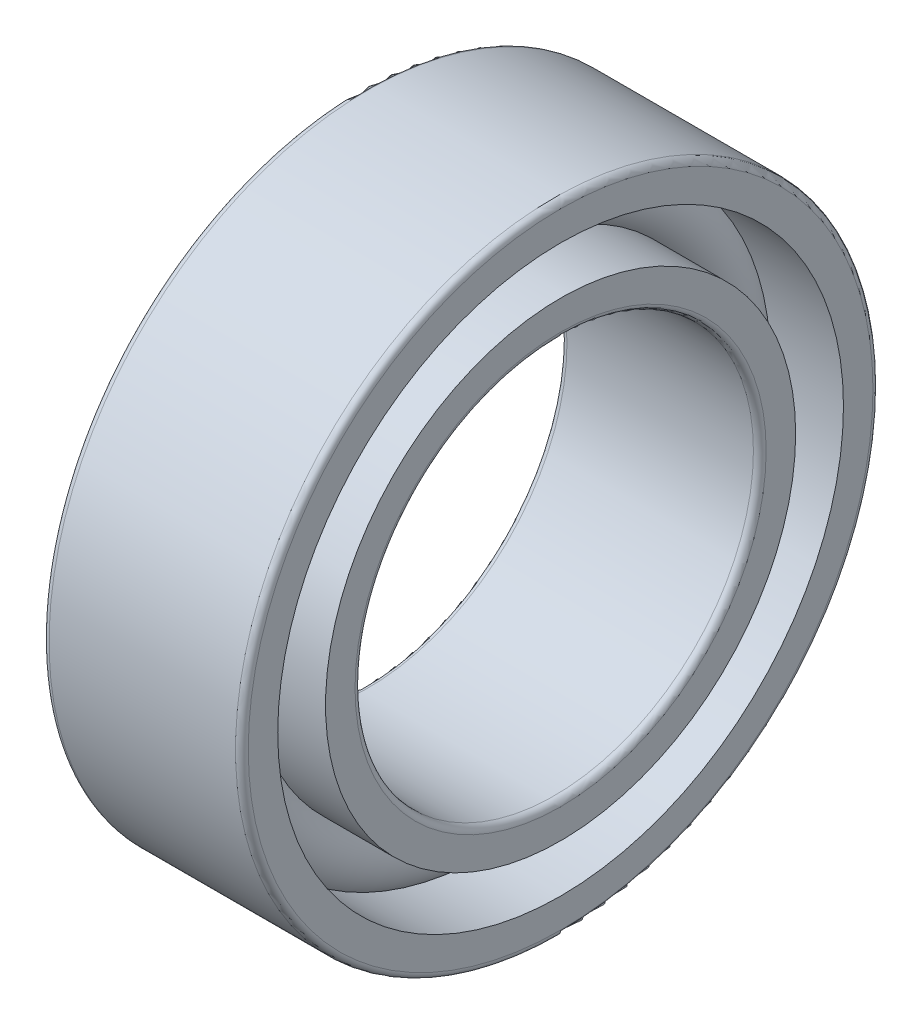
SolidWorks part; units mm, degrees
ref_plane "Plane1" through (0, 0, 0) normal (0, 0, 1) x (1, 0, 0)
ref_plane "Plane2" through (0, 0, 0) normal (0, 1, 0) x (1, 0, 0)
ref_plane "Plane3" through (0, 0, 0) normal (1, 0, 0) x (0, 0, -1)
sketch "Clipboard" plane through (0, 0, 0) normal (0, 0, 1) x (1, 0, 0)
  line L0 (-10, 0) -> (10, 0) construction
  line L1 (0, 0) -> (22.3471, -0.7804)
  line L2 (0, 0) -> (3.248, 0.1134)
  line L3 (0, 0) -> (22.3471, -0.7804)
  line L4 (0, 0) -> (-22.3573, -0.3902)
  dimension "BallCLRad" = 3.25
sketch "CagSpiSke" plane through (0, 0, 0) normal (0, 0, 1) x (1, 0, 0)
  line L0 (0.045, 3.175) -> (0.045, 3.325)
  line L1 (0.045, 3.325) -> (-0.045, 3.325)
  line L2 (-0.045, 3.325) -> (-0.045, 3.175)
  line L3 (-0.045, 3.175) -> (0.045, 3.175)
  line L4 (-20.6375, 0) -> (20.6375, 0) construction
  line L5 (0, 0) -> (0, 23.7692) construction
  dimension "OD" = 6.65
  dimension "ID" = 6.35
revolve "CageSpine" add sketch "CagSpiSke" angle 0.001 about L4 reverse direction yes
ref_axis "Axis1" through (-50, 0, 0) along (1, 0, 0)
sketch "CagBalSke" plane through (0, 0, 0) normal (0, 0, 1) x (1, 0, 0)
  line L0 (-0.495, 3.25) -> (0.495, 3.25)
  line L1 (-1.905, 3.25) -> (1.905, 3.25) construction
  line L2 (-10, 0) -> (10, 0) construction
  line L3 (0, 0) -> (0, 24) construction
  arc A0 (0.495, 3.25) -> (-0.495, 3.25) centre (0, 3.25) cw
  dimension "BallCLRad" = 3.25
revolve "CageBall" [suppressed] add sketch "CagBalSke" angle 360 about L1 reverse direction yes
pattern_circular "CageBalls" [suppressed] count 2 every 180 about axis through (-50, 0, 0) along (1, 0, 0)
sketch "CagTrmODSke" plane through (0, 0, 0) normal (0, 0, 1) x (1, 0, 0)
  line L0 (0.496, 3.325) -> (0.496, 3.746)
  line L1 (0.496, 3.746) -> (-0.496, 3.746)
  line L2 (-0.496, 3.746) -> (-0.496, 3.325)
  line L3 (-0.496, 3.325) -> (0.496, 3.325)
  line L4 (-20.6375, 0) -> (20.6375, 0) construction
  line L5 (0, 0) -> (0, 25) construction
  dimension "Width" = 0.992
  dimension "ID" = 6.65
  dimension "OD" = 7.492
revolve "CageTrimOD" [suppressed] cut sketch "CagTrmODSke" angle 360 about L4 reverse direction yes
sketch "CagTrmIDSke" plane through (0, 0, 0) normal (0, 0, 1) x (1, 0, 0)
  line L0 (0.496, 2.756) -> (0.496, 3.175)
  line L1 (0.496, 3.175) -> (-0.496, 3.175)
  line L2 (-0.496, 3.175) -> (-0.496, 2.756)
  line L3 (-0.496, 2.756) -> (0.496, 2.756)
  line L4 (-20.6375, 0) -> (20.6375, 0) construction
  line L5 (0, 0) -> (0, 25) construction
  dimension "Width" = 0.992
  dimension "ID" = 5.512
  dimension "OD" = 6.35
revolve "CageTrimID" [suppressed] cut sketch "CagTrmIDSke" angle 360 about L4 reverse direction yes
sketch "BalSimSke" plane through (0, 0, 0) normal (0, 0, 1) x (1, 0, 0)
  line L0 (-10, 0) -> (10, 0) construction
  line L1 (-10, 3.25) -> (10, 3.25) construction
  line L2 (0, 0) -> (0, 23) construction
  circle A0 centre (0, 3.25) radius 0.45
  dimension "BallCLRad" = 3.25
  dimension "Ball_diameter" = 0.9
revolve "BallsSimplified" add sketch "BalSimSke" angle 360 about L0
sketch "BalDetSke" plane through (0, 0, 0) normal (0, 0, 1) x (1, 0, 0)
  line L0 (-0.45, 3.25) -> (0.45, 3.25)
  line L1 (-1.905, 3.25) -> (1.905, 3.25) construction
  line L2 (0, 0) -> (0, 25) construction
  arc A0 (0.45, 3.25) -> (-0.45, 3.25) centre (0, 3.25) cw
  dimension "BallCLRad" = 3.25
  dimension "Ball_diameter" = 0.9
revolve "BallDetailed" [suppressed] add sketch "BalDetSke" angle 360 about L1 reverse direction yes
sketch "InnRacSke" plane through (0, 0, 0) normal (0, 0, 1) x (1, 0, 0)
  line L0 (-0.301, 2.95) -> (-1.25, 2.95)
  line L1 (-1.25, 2.95) -> (-1.25, 2.58)
  line L2 (-1.17, 2.5) -> (1.17, 2.5)
  line L3 (1.25, 2.58) -> (1.25, 2.95)
  line L4 (1.25, 2.95) -> (0.301, 2.95)
  line L5 (-20.6375, 0) -> (20.6375, 0) construction
  line L6 (0, 0) -> (0, 30) construction
  arc A0 (-1.25, 2.58) -> (-1.17, 2.5) centre (-1.17, 2.58) ccw
  arc A1 (1.17, 2.5) -> (1.25, 2.58) centre (1.17, 2.58) ccw
  arc A2 (0.301, 2.95) -> (-0.301, 2.95) centre (0, 3.25) cw
  dimension "BallCLRad" = 3.25
  dimension "Fillet_radius" = 0.08
  dimension "Ball_diameter" = 0.85
  dimension "ID" = 5
  dimension "OD" = 5.9
  dimension "Width" = 2.5
revolve "InnerRace" add sketch "InnRacSke" angle 360 about L5 reverse direction yes
sketch "OutRacSke" plane through (0, 0, 0) normal (0, 0, 1) x (1, 0, 0)
  line L0 (-0.301, 3.55) -> (-1.25, 3.55)
  line L1 (-1.25, 3.55) -> (-1.25, 3.92)
  line L2 (-1.17, 4) -> (1.17, 4)
  line L3 (1.25, 3.92) -> (1.25, 3.55)
  line L4 (1.25, 3.55) -> (0.301, 3.55)
  line L5 (-20.6375, 0) -> (20.6375, 0) construction
  line L6 (0, 0) -> (0, 30) construction
  arc A0 (-1.25, 3.92) -> (-1.17, 4) centre (-1.17, 3.92) cw
  arc A1 (1.17, 4) -> (1.25, 3.92) centre (1.17, 3.92) cw
  arc A2 (0.301, 3.55) -> (-0.301, 3.55) centre (0, 3.25) ccw
  dimension "BallCLRad" = 3.25
  dimension "Fillet_radius" = 0.08
  dimension "Ball_diameter" = 0.85
  dimension "Width" = 2.5
revolve "OuterRace" add sketch "OutRacSke" angle 360 about L5 reverse direction yes
pattern_circular "BallsDetailed" [suppressed] count 2 every 180 about axis through (-50, 0, 0) along (1, 0, 0)
equation "\"BallCLRad@Clipboard\" = ( \"OD@OutRacSke\" + \"ID@InnRacSke\" ) / 4"
equation "\"BallCLRad@BalSimSke\" = \"BallCLRad@Clipboard\""
equation "\"BallCLRad@BalDetSke\" = \"BallCLRad@Clipboard\""
equation "\"BallCLRad@InnRacSke\" = \"BallCLRad@Clipboard\""
equation "\"BallCLRad@OutRacSke\" = \"BallCLRad@Clipboard\""
equation "\"Ball_diameter@InnRacSke\" = \"Ball_diameter@BalDetSke\" - 0.05"
equation "\"Ball_diameter@OutRacSke\" = \"Ball_diameter@BalDetSke\" - 0.05"
equation "\"Ball_diameter@BalSimSke\" = \"Ball_diameter@BalDetSke\""
equation "\"Width@OutRacSke\" = \"Width@InnRacSke\""
equation "\"Fillet_radius@OutRacSke\" = \"Fillet_radius@InnRacSke\""
equation "\"Max_count@Clipboard\" = int( 3.14159265 / atn(( \"Ball_diameter@BalDetSke\" / 2) / sqr( \"BallCLRad@Clipboard\"  *  \"BallCLRad@Clipboard\" - ( \"Ball_diameter@BalDetSke\" / 2) *  ( \"Ball_diameter@BalDetSke\" / 2))))"
equation "\"Max_count@Clipboard\" = ((sgn( \"Max_count@Clipboard\" - \"Count@Clipboard\" )-1)*( \"Max_count@Clipboard\" - \"Count@Clipboard\" ))/-2+ \"Count@Clipboard\""
equation "\"Count@BallsDetailed\" = int( \"Show_count@Clipboard\" ) "
equation "\"Count@BallsDetailed\" = ((sgn( \"Count@BallsDetailed\" - \"Max_count@Clipboard\" )-1)*( \"Count@BallsDetailed\" - \"Max_count@Clipboard\" ))/-2+ \"Max_count@Clipboard\""
equation "\"Count@BallsDetailed\" = ((sgn( \"Count@BallsDetailed\" - \"Min_count@Clipboard\" )+1)*( \"Count@BallsDetailed\" - \"Min_count@Clipboard\"))/2 +\"Min_count@Clipboard\""
equation "\"Angle@BallsDetailed\" = 360.0 / \"Max_count@Clipboard\""
equation "\"BallCLRad@CagBalSke\" = \"BallCLRad@Clipboard\""
equation "\"Count@CageBalls\" = \"Count@BallsDetailed\""
equation "\"Angle@CageBalls\" = \"Angle@BallsDetailed\""
equation "\"Angle@CageSpine\" =  \"Angle@CageBalls\" * ( \"Count@CageBalls\" -1 + int( \"Count@CageBalls\" / \"Max_count@Clipboard\" ) )  + 0.001 -  int( \"Count@CageBalls\" / \"Max_count@Clipboard\" ) * 0.001"
equation "\"Angle@CageSpine\" =  \"Angle@CageSpine\" * int( \"Min_count@Clipboard\" / 2) + int(1 / \"Min_count@Clipboard\")  * 0.001"
equation "\"CageWallOD@CagBalSke\" =  \"Ball_diameter@BalDetSke\" * 1.1"
equation "\"Thickness@CagSpiSke\" =  \"Ball_diameter@BalDetSke\" * 0.1"
equation "\"OD@CagTrmODSke\" = \"BallCLRad@Clipboard\" * 2 + \"CageWallOD@CagBalSke\" + 0.002"
equation "\"ID@CagTrmODSke\" = \"BallCLRad@Clipboard\" * 2 + \"Ball_diameter@BalDetSke\" / 6"
equation "\"OD@CagTrmIDSke\" = \"BallCLRad@Clipboard\" * 2 - \"Ball_diameter@BalDetSke\" / 6"
equation "\"ID@CagTrmIDSke\" = \"BallCLRad@Clipboard\" * 2 - \"CageWallOD@CagBalSke\" + 0.002"
equation "\"OD@CagSpiSke\" = \"ID@CagTrmODSke\""
equation "\"ID@CagSpiSke\" = \"OD@CagTrmIDSke\""
equation "\"Width@CagTrmODSke\" = \"CageWallOD@CagBalSke\" + 0.002"
equation "\"Width@CagTrmIDSke\" = \"CageWallOD@CagBalSke\" + 0.002"
